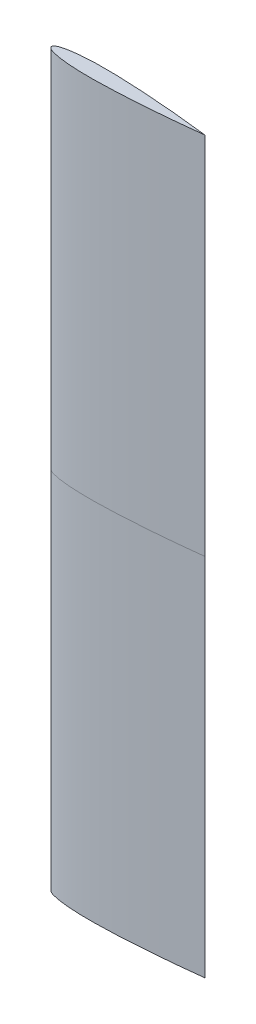
SolidWorks part; units mm, degrees
ref_plane "Front Plane" through (0, 0, 0) normal (0, 0, 1) x (1, 0, 0)
ref_plane "Top Plane" through (0, 0, 0) normal (0, 1, 0) x (1, 0, 0)
ref_plane "Right Plane" through (0, 0, 0) normal (1, 0, 0) x (0, 0, -1)
sketch "rootSketch" plane through (0, 0, 0) normal (0, 1, 0) x (1, 0, 0)
  line L0 (0, 0) -> (1500, 0) construction
  line L2 (62.5, -12.5) -> (62.5, 12.5) construction
  line L3 (0, 0) -> (250, 0) construction
  spline S0 degree 4 poles (0, 0) (0.0001, 0.1958) (0.0283, 0.4928) (0.1272, 0.8942) (0.3432, 1.3785) (0.5943, 1.7936) (0.9501, 2.2499) (1.4714, 2.7798) (2.2793, 3.431) (3.603, 4.2687) (5.8708, 5.3669) (9.9301, 6.8174) (17.1522, 8.6122) (28.7203, 10.4479) (44.1685, 11.8206) (62.5424, 12.5283) (82.3338, 12.5685) (99.645, 12.1538) (114.4748, 11.5582) (126.8265, 10.9293) (136.7043, 10.3557) (146.5777, 9.719) (156.4482, 9.025) (166.3131, 8.2785) (176.1771, 7.4825) (186.0322, 6.64) (194.66, 5.8619) (202.0396, 5.168) (208.2081, 4.5682) (213.1048, 4.0811) (218.075, 3.5732) (222.9115, 3.0692) (227.9707, 2.5258) (232.6561, 2.0146) (237.9564, 1.4157) (242.2332, 0.927) (247.662, 0.283) (250.7934, -0.0947) (254.769, -0.5833) (257.795, -0.9625) (260.9541, -1.3643) (264.0646, -1.7671) (267.1971, -2.1794) (270.3145, -2.5971) (272.6607, -2.9169) (274.2188, -3.1319) (275.0002, -3.2403) knots 0 0 0 0 0 0.002791 0.004281 0.005883 0.007585 0.009735 0.012562 0.016522 0.022438 0.032158 0.048634 0.078249 0.129037 0.199997 0.270957 0.341918 0.412878 0.448358 0.483838 0.519318 0.554798 0.590279 0.625759 0.661239 0.696719 0.732199 0.749939 0.767679 0.785419 0.80316 0.8209 0.83864 0.85638 0.87412 0.89186 0.9096 0.9209 0.9322 0.9435 0.9548 0.9661 0.9774 0.9887 1 1 1 1 1 construction
  spline S1 degree 4 poles (0, 0) (0.0001, 0.1958) (0.0283, 0.4928) (0.1272, 0.8942) (0.3432, 1.3785) (0.5943, 1.7936) (0.9501, 2.2499) (1.4714, 2.7798) (2.2793, 3.431) (3.603, 4.2687) (5.8708, 5.3669) (9.9301, 6.8174) (17.1522, 8.6122) (28.7203, 10.4479) (44.1685, 11.8206) (62.5424, 12.5283) (82.3338, 12.5685) (99.645, 12.1538) (114.4748, 11.5582) (126.8265, 10.9293) (136.7043, 10.3557) (146.5777, 9.719) (156.4482, 9.025) (166.3131, 8.2785) (176.1771, 7.4825) (186.0322, 6.64) (194.66, 5.8619) (202.0396, 5.168) (208.2081, 4.5682) (213.1048, 4.0811) (218.075, 3.5732) (222.9115, 3.0692) (227.9707, 2.5258) (232.6561, 2.0146) (237.9564, 1.4157) (242.2332, 0.927) (246.7112, 0.3958) (248.8832, 0.1353) (250, 0) knots 0 0 0 0 0 0.002791 0.004281 0.005883 0.007585 0.009735 0.012562 0.016522 0.022438 0.032158 0.048634 0.078249 0.129037 0.199997 0.270957 0.341918 0.412878 0.448358 0.483838 0.519318 0.554798 0.590279 0.625759 0.661239 0.696719 0.732199 0.749939 0.767679 0.785419 0.80316 0.8209 0.83864 0.85638 0.87412 0.89186 0.9096 0.9096 0.9096 0.9096 0.9096
  spline S2 degree 4 poles (0, 0) (0.0001, -0.1958) (0.0283, -0.4928) (0.1272, -0.8942) (0.3432, -1.3785) (0.5943, -1.7936) (0.9501, -2.2499) (1.4714, -2.7798) (2.2793, -3.431) (3.603, -4.2687) (5.8708, -5.3669) (9.9301, -6.8174) (17.1522, -8.6122) (28.7203, -10.4479) (44.1685, -11.8206) (62.5424, -12.5283) (82.3338, -12.5685) (99.645, -12.1538) (114.4748, -11.5582) (126.8265, -10.9293) (136.7043, -10.3557) (146.5777, -9.719) (156.4482, -9.025) (166.3131, -8.2785) (176.1771, -7.4825) (186.0322, -6.64) (194.66, -5.8619) (202.0396, -5.168) (208.2081, -4.5682) (213.1048, -4.0811) (218.075, -3.5732) (222.9115, -3.0692) (227.9707, -2.5258) (232.6561, -2.0146) (237.9564, -1.4157) (242.2332, -0.927) (247.662, -0.283) (250.7934, 0.0947) (254.769, 0.5833) (257.795, 0.9625) (260.9541, 1.3643) (264.0646, 1.7671) (267.1971, 2.1794) (270.3145, 2.5971) (272.6607, 2.9169) (274.2188, 3.1319) (275.0002, 3.2403) knots 0 0 0 0 0 0.002791 0.004281 0.005883 0.007585 0.009735 0.012562 0.016522 0.022438 0.032158 0.048634 0.078249 0.129037 0.199997 0.270957 0.341918 0.412878 0.448358 0.483838 0.519318 0.554798 0.590279 0.625759 0.661239 0.696719 0.732199 0.749939 0.767679 0.785419 0.80316 0.8209 0.83864 0.85638 0.87412 0.89186 0.9096 0.9209 0.9322 0.9435 0.9548 0.9661 0.9774 0.9887 1 1 1 1 1 construction
  spline S3 degree 4 poles (0, 0) (0.0001, -0.1958) (0.0283, -0.4928) (0.1272, -0.8942) (0.3432, -1.3785) (0.5943, -1.7936) (0.9501, -2.2499) (1.4714, -2.7798) (2.2793, -3.431) (3.603, -4.2687) (5.8708, -5.3669) (9.9301, -6.8174) (17.1522, -8.6122) (28.7203, -10.4479) (44.1685, -11.8206) (62.5424, -12.5283) (82.3338, -12.5685) (99.645, -12.1538) (114.4748, -11.5582) (126.8265, -10.9293) (136.7043, -10.3557) (146.5777, -9.719) (156.4482, -9.025) (166.3131, -8.2785) (176.1771, -7.4825) (186.0322, -6.64) (194.66, -5.8619) (202.0396, -5.168) (208.2081, -4.5682) (213.1048, -4.0811) (218.075, -3.5732) (222.9115, -3.0692) (227.9707, -2.5258) (232.6561, -2.0146) (237.9564, -1.4157) (242.2332, -0.927) (246.7112, -0.3958) (248.8832, -0.1353) (250, 0) knots 0 0 0 0 0 0.002791 0.004281 0.005883 0.007585 0.009735 0.012562 0.016522 0.022438 0.032158 0.048634 0.078249 0.129037 0.199997 0.270957 0.341918 0.412878 0.448358 0.483838 0.519318 0.554798 0.590279 0.625759 0.661239 0.696719 0.732199 0.749939 0.767679 0.785419 0.80316 0.8209 0.83864 0.85638 0.87412 0.89186 0.9096 0.9096 0.9096 0.9096 0.9096
  point P10 (62.5, 0)
  dimension "incidenceAngle" = 0
  dimension "rootChord" = 250
  dimension "rootQuarterChord" = 62.5
  dimension "rootMaxThickness" = 25
ref_plane "Plane1" through (0, 594, 0) normal (0, 1, 0) x (1, 0, 0)
sketch "tipSketch" plane through (0, 594, 0) normal (0, 1, 0) x (1, 0, 0)
  line L0 (218.7894, 0) -> (520.1012, 0) construction
  line L3 (0, 0) -> (250, 0) construction
  line L4 (62.5, -12.5) -> (62.5, 12.5) construction
  spline S0 degree 4 poles (0, 0) (0.0001, 0.1958) (0.0283, 0.4928) (0.1272, 0.8942) (0.3432, 1.3785) (0.5943, 1.7936) (0.9501, 2.2499) (1.4714, 2.7798) (2.2793, 3.431) (3.603, 4.2687) (5.8708, 5.3669) (9.9301, 6.8174) (17.1522, 8.6122) (28.7203, 10.4479) (44.1685, 11.8206) (62.5424, 12.5283) (82.3338, 12.5685) (99.645, 12.1538) (114.4748, 11.5582) (126.8265, 10.9293) (136.7043, 10.3557) (146.5777, 9.719) (156.4482, 9.025) (166.3131, 8.2785) (176.1771, 7.4825) (186.0322, 6.64) (194.66, 5.8619) (202.0396, 5.168) (208.2081, 4.5682) (213.1048, 4.0811) (218.075, 3.5732) (222.9115, 3.0692) (227.9707, 2.5258) (232.6561, 2.0146) (237.9564, 1.4157) (242.2332, 0.927) (247.662, 0.283) (250.7934, -0.0947) (254.769, -0.5833) (257.795, -0.9625) (260.9541, -1.3643) (264.0646, -1.7671) (267.1971, -2.1794) (270.3145, -2.5971) (272.6607, -2.9169) (274.2188, -3.1319) (275.0002, -3.2403) knots 0 0 0 0 0 0.002791 0.004281 0.005883 0.007585 0.009735 0.012562 0.016522 0.022438 0.032158 0.048634 0.078249 0.129037 0.199997 0.270957 0.341918 0.412878 0.448358 0.483838 0.519318 0.554798 0.590279 0.625759 0.661239 0.696719 0.732199 0.749939 0.767679 0.785419 0.80316 0.8209 0.83864 0.85638 0.87412 0.89186 0.9096 0.9209 0.9322 0.9435 0.9548 0.9661 0.9774 0.9887 1 1 1 1 1 construction
  spline S1 degree 4 poles (0, 0) (0.0001, 0.1958) (0.0283, 0.4928) (0.1272, 0.8942) (0.3432, 1.3785) (0.5943, 1.7936) (0.9501, 2.2499) (1.4714, 2.7798) (2.2793, 3.431) (3.603, 4.2687) (5.8708, 5.3669) (9.9301, 6.8174) (17.1522, 8.6122) (28.7203, 10.4479) (44.1685, 11.8206) (62.5424, 12.5283) (82.3338, 12.5685) (99.645, 12.1538) (114.4748, 11.5582) (126.8265, 10.9293) (136.7043, 10.3557) (146.5777, 9.719) (156.4482, 9.025) (166.3131, 8.2785) (176.1771, 7.4825) (186.0322, 6.64) (194.66, 5.8619) (202.0396, 5.168) (208.2081, 4.5682) (213.1048, 4.0811) (218.075, 3.5732) (222.9115, 3.0692) (227.9707, 2.5258) (232.6561, 2.0146) (237.9564, 1.4157) (242.2332, 0.927) (246.7112, 0.3958) (248.8832, 0.1353) (250, 0) knots 0 0 0 0 0 0.002791 0.004281 0.005883 0.007585 0.009735 0.012562 0.016522 0.022438 0.032158 0.048634 0.078249 0.129037 0.199997 0.270957 0.341918 0.412878 0.448358 0.483838 0.519318 0.554798 0.590279 0.625759 0.661239 0.696719 0.732199 0.749939 0.767679 0.785419 0.80316 0.8209 0.83864 0.85638 0.87412 0.89186 0.9096 0.9096 0.9096 0.9096 0.9096
  spline S2 degree 4 poles (0, 0) (0.0001, -0.1958) (0.0283, -0.4928) (0.1272, -0.8942) (0.3432, -1.3785) (0.5943, -1.7936) (0.9501, -2.2499) (1.4714, -2.7798) (2.2793, -3.431) (3.603, -4.2687) (5.8708, -5.3669) (9.9301, -6.8174) (17.1522, -8.6122) (28.7203, -10.4479) (44.1685, -11.8206) (62.5424, -12.5283) (82.3338, -12.5685) (99.645, -12.1538) (114.4748, -11.5582) (126.8265, -10.9293) (136.7043, -10.3557) (146.5777, -9.719) (156.4482, -9.025) (166.3131, -8.2785) (176.1771, -7.4825) (186.0322, -6.64) (194.66, -5.8619) (202.0396, -5.168) (208.2081, -4.5682) (213.1048, -4.0811) (218.075, -3.5732) (222.9115, -3.0692) (227.9707, -2.5258) (232.6561, -2.0146) (237.9564, -1.4157) (242.2332, -0.927) (247.662, -0.283) (250.7934, 0.0947) (254.769, 0.5833) (257.795, 0.9625) (260.9541, 1.3643) (264.0646, 1.7671) (267.1971, 2.1794) (270.3145, 2.5971) (272.6607, 2.9169) (274.2188, 3.1319) (275.0002, 3.2403) knots 0 0 0 0 0 0.002791 0.004281 0.005883 0.007585 0.009735 0.012562 0.016522 0.022438 0.032158 0.048634 0.078249 0.129037 0.199997 0.270957 0.341918 0.412878 0.448358 0.483838 0.519318 0.554798 0.590279 0.625759 0.661239 0.696719 0.732199 0.749939 0.767679 0.785419 0.80316 0.8209 0.83864 0.85638 0.87412 0.89186 0.9096 0.9209 0.9322 0.9435 0.9548 0.9661 0.9774 0.9887 1 1 1 1 1 construction
  spline S3 degree 4 poles (0, 0) (0.0001, -0.1958) (0.0283, -0.4928) (0.1272, -0.8942) (0.3432, -1.3785) (0.5943, -1.7936) (0.9501, -2.2499) (1.4714, -2.7798) (2.2793, -3.431) (3.603, -4.2687) (5.8708, -5.3669) (9.9301, -6.8174) (17.1522, -8.6122) (28.7203, -10.4479) (44.1685, -11.8206) (62.5424, -12.5283) (82.3338, -12.5685) (99.645, -12.1538) (114.4748, -11.5582) (126.8265, -10.9293) (136.7043, -10.3557) (146.5777, -9.719) (156.4482, -9.025) (166.3131, -8.2785) (176.1771, -7.4825) (186.0322, -6.64) (194.66, -5.8619) (202.0396, -5.168) (208.2081, -4.5682) (213.1048, -4.0811) (218.075, -3.5732) (222.9115, -3.0692) (227.9707, -2.5258) (232.6561, -2.0146) (237.9564, -1.4157) (242.2332, -0.927) (246.7112, -0.3958) (248.8832, -0.1353) (250, 0) knots 0 0 0 0 0 0.002791 0.004281 0.005883 0.007585 0.009735 0.012562 0.016522 0.022438 0.032158 0.048634 0.078249 0.129037 0.199997 0.270957 0.341918 0.412878 0.448358 0.483838 0.519318 0.554798 0.590279 0.625759 0.661239 0.696719 0.732199 0.749939 0.767679 0.785419 0.80316 0.8209 0.83864 0.85638 0.87412 0.89186 0.9096 0.9096 0.9096 0.9096 0.9096
  point P10 (62.5, 0)
  dimension "incidenceAngle" = 0
  dimension "tipChord" = 250
  dimension "tipQuarterChord" = 62.5
  dimension "tipMaxThickness" = 25
  dimension "sweepOffset" = 0
loft "Loft1" add profiles "rootSketch", "tipSketch"
mirror "Mirror1" about plane through (0, 0, 0) normal (0, 1, 0) of "Loft1"
ref_plane "Plane2" through (250, 0, 0) normal (1, 0, 0) x (0, 0, -1)
sketch "elevatorSketch" plane through (0, 0, 0) normal (0, 0, 1) x (1, 0, 0)
  line L0 (151.188, 0) -> (151.188, 444.312)
  line L1 (0, 445.5) -> (150, 445.5) construction
  line L2 (0, 0) -> (150, 0) construction
  line L3 (0, 0) -> (250, 0) construction
  line L4 (150, 0) -> (150, 445.5)
  line L5 (151.188, 444.312) -> (400, 444.312)
  line L7 (150, 445.5) -> (400, 445.5)
  line L8 (150, 0) -> (151.188, 0)
  line L9 (400, 445.5) -> (400, 444.312)
  dimension "elevatorEndyLoc" = 445.5
  dimension "elevatorEndxLoc" = 150
  dimension "D1" = 150
  dimension "D2" = 250
  dimension "D3" = 1.188
extrude "Cut-Extrude2" [suppressed] cut sketch "elevatorSketch" against normal blind 200 and the other way blind 200 contours L0 L5 L9 L7 L4 L8
mirror "Mirror2" [suppressed] about plane through (0, 0, 0) normal (0, 1, 0)
equation "\"rootChord\"= 0.25"
equation "\"NACAairfoil\"= 0010"
equation "\"incidentAngle\"= 0"
equation "\"aspectRatio\"= 6.8376"
equation "\"taperRatio\"= 1"
equation "\"sweepAngle\"= 0'H-stab sweep angle"
equation "\"rootChord@rootSketch\"=(\"rootChord\"+\"rootChord\")/2"
equation "\"rootQuarterChord@rootSketch\"= \"rootChord@rootSketch\" / 4"
equation "\"rootMaxThickness@rootSketch\" = \"rootChord\" * \"NACAairfoil\" / 100"
equation "\"halfSpan@Plane1\"= \"halfSpan\""
equation "\"tipQuarterChord@tipSketch\"=\"tipChord@tipSketch\"/4"
equation "\"tipMaxThickness@tipSketch\"=\"tipChord@tipSketch\"*\"NACAairfoil\"/100"
equation "\"rootChord@Plane2\"=\"rootChord@rootSketch\""
equation "\"elevatorWidth\"= 0.75'Elevator width as a percentage of H-stab span"
equation "\"elevatorEndyLoc@elevatorSketch\"=\"elevatorWidth\"*\"halfSpan@Plane1\""
equation "\"elevatorEndxLoc@elevatorSketch\"=\"elevatorEndyLoc@elevatorSketch\" * tan ( \"sweepAngle\" )  + 0.6 *  ( \"rootChord@rootSketch\" + \"elevatorEndyLoc@elevatorSketch\" *  (  (  ( \"tipChord@tipSketch\" - \"rootChord@rootSketch\" )  / \"halfSpan@Plane1\" )  )  )"
equation "\"D1@elevatorSketch\"=0.6*\"rootChord@rootSketch\""
equation "\"D2@elevatorSketch\"=1*\"rootChord@rootSketch\""
equation "\"D3@elevatorSketch\" = \"halfSpan\" / 500"
equation "\"halfSpan\"= \"turbineDiameter\" * 1.5'H-stab half Span"
equation "\"sweepOffset@tipSketch\" = \"halfSpan\" * tan ( \"sweepAngle\" ) "
equation "\"incidenceAngle@rootSketch\"=\"incidentAngle\""
equation "\"turbineDiameter\"= .396"
equation "\"tipChord@tipSketch\"=\"rootChord\"*\"taperRatio\""
equation "\"incidenceAngle@tipSketch\"=\"incidentAngle\""
